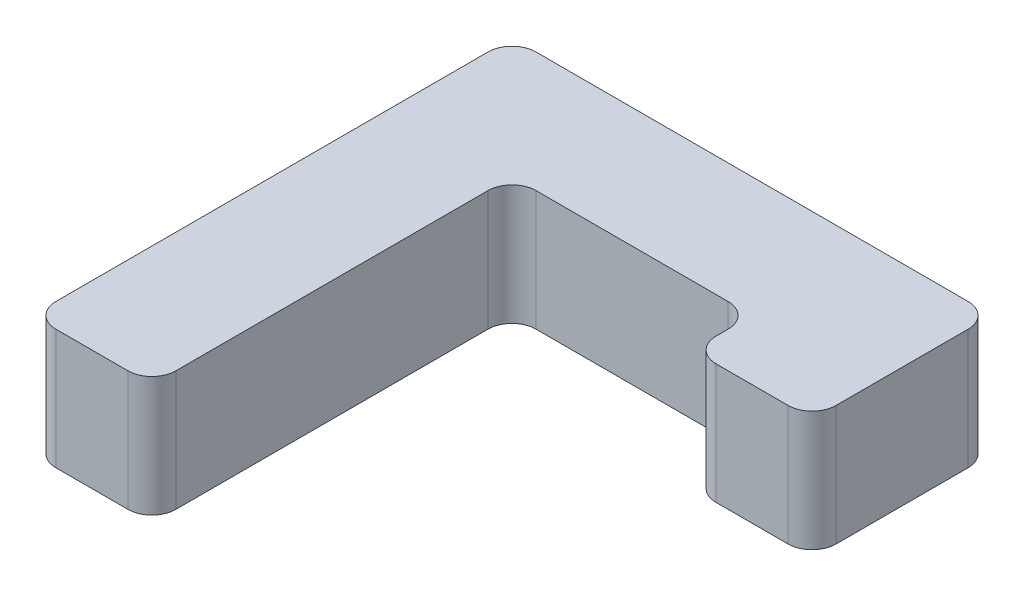
SolidWorks part; units mm, degrees
ref_plane "Front Plane" through (0, 0, 0) normal (0, 0, 1) x (1, 0, 0)
ref_plane "Top Plane" through (0, 0, 0) normal (0, 1, 0) x (1, 0, 0)
ref_plane "Right Plane" through (0, 0, 0) normal (1, 0, 0) x (0, 0, -1)
sketch "Sketch1" plane through (0, 0, 0) normal (0, 1, 0) x (1, 0, 0)
  line L0 (0, 0) -> (0, 50.8)
  line L1 (0, 50.8) -> (50.8, 50.8)
  line L2 (50.8, 50.8) -> (50.8, 31.75)
  line L3 (50.8, 31.75) -> (38.1, 31.75)
  line L4 (38.1, 31.75) -> (38.1, 38.1)
  line L5 (38.1, 38.1) -> (12.7, 38.1)
  line L6 (12.7, 38.1) -> (12.7, 0)
  line L7 (12.7, 0) -> (0, 0)
  dimension "D1" = 25.4
  dimension "D2" = 50.8
  dimension "D3" = 12.7
  dimension "D4" = 12.7
  dimension "D5" = 19.05
  dimension "D6" = 50.8
extrude "Boss-Extrude1" add sketch "Sketch1" along normal blind 12.7
fillet "Fillet1" radius 2.54 8 edges at (50.8, 6.35, -50.8) (38.1, 6.35, -38.1) (50.8, 6.35, -31.75) (38.1, 6.35, -31.75) (12.7, 6.35, 0) (0, 6.35, 0) (12.7, 6.35, -38.1) (0, 6.35, -50.8)
ref_plane "Plane1" through (25.4, 0, 0) normal (1, 0, 0) x (0, 0, -1)
